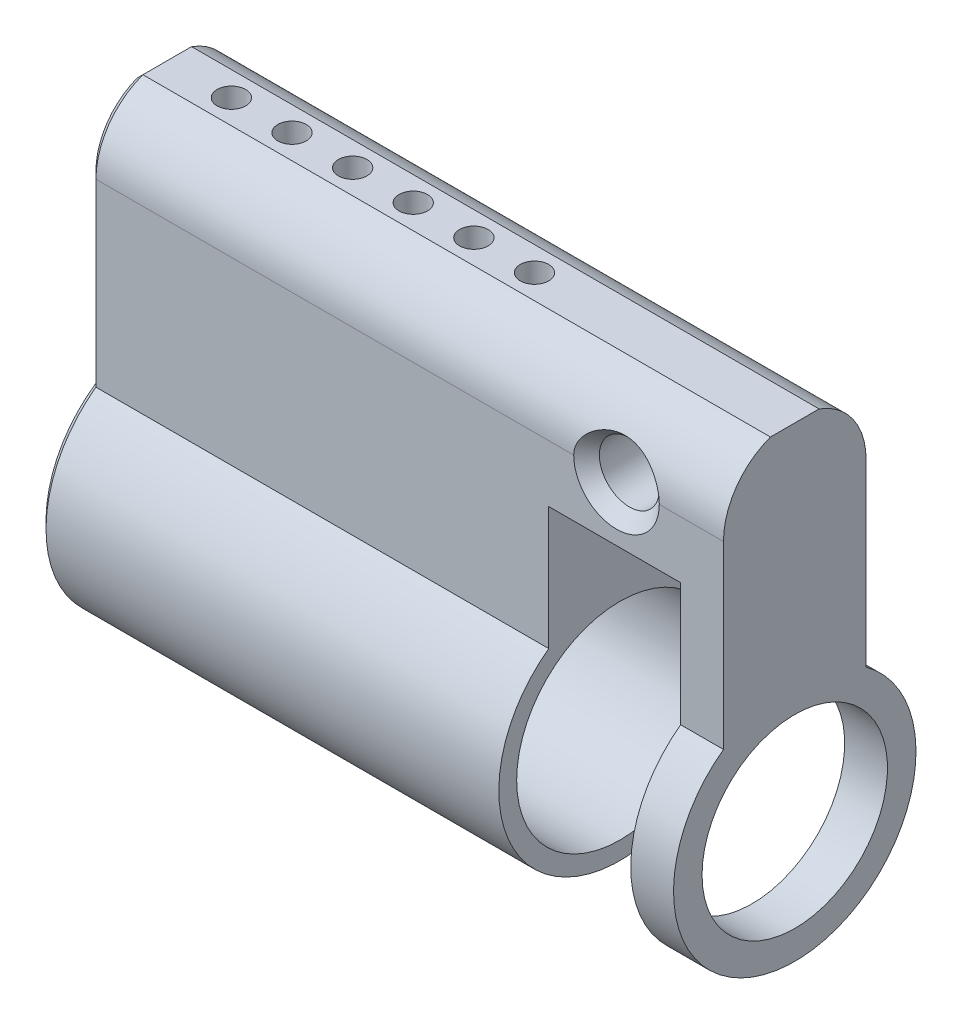
SolidWorks part; units mm, degrees
ref_plane "Front Plane" through (0, 0, 0) normal (0, 0, 1) x (1, 0, 0)
ref_plane "Top Plane" through (0, 0, 0) normal (0, 1, 0) x (1, 0, 0)
ref_plane "Right Plane" through (0, 0, 0) normal (1, 0, 0) x (0, 0, -1)
sketch "Sketch1" plane through (0, 0, 0) normal (1, 0, 0) x (0, 0, -1)
  line L0 (0, 0) -> (0, 19.5) construction
  line L1 (-5, 19.5) -> (5, 19.5) construction
  line L2 (-5, 19.5) -> (-5, 6.8739)
  line L3 (5, 19.5) -> (5, 6.8739)
  line L4 (-1.7059, 24.2) -> (1.7059, 24.2)
  arc A0 (-5, 6.8739) -> (5, 6.8739) centre (0, 0) ccw
  arc A1 (5, 19.5) -> (1.7059, 24.2) centre (0, 19.5) ccw
  arc A3 (-1.7059, 24.2) -> (-5, 19.5) centre (0, 19.5) ccw
  dimension "D1" = 17
  dimension "D2" = 5
  dimension "D3" = 33
  dimension "D5" = 0.3
  dimension "D6" = 3.4117
extrude "euro cylinder outline" add sketch "Sketch1" along normal blind 44.5
sketch "Sketch9" plane through (0, 0, 0) normal (-1, 0, 0) x (0, 0, 1)
  circle A0 centre (0, 0) radius 7.25
  dimension "D1" = 14.5
extrude "bore for core" cut sketch "Sketch9" against normal blind 37
sketch "Sketch2" plane through (0, 0, 0) normal (0, 1, 0) x (1, 0, 0)
  line L0 (0, 5) -> (0, 1.7059) construction
  circle A0 centre (5, 0) radius 1
  dimension "D1" = 2
  dimension "D2" = 5
extrude "hole for pin" cut sketch "Sketch2" along normal blind 35
pattern_linear "LPattern of 6" count 6 spacing 4.25 along (1, 0, 0) of "hole for pin"
sketch "Sketch3" plane through (0, 0, 5) normal (0, 0, 1) x (1, 0, 0)
  line L0 (44.5, 19.5) -> (44.5, 6.8739) construction
  line L1 (32.25, -8.5) -> (41.5, -8.5)
  line L2 (32.25, -8.5) -> (32.25, 15.5)
  line L3 (32.25, 15.5) -> (41.5, 15.5)
  line L4 (41.5, -8.5) -> (41.5, 15.5)
  line L5 (44.5, 24.2) -> (0, 24.2) construction
  dimension "D1" = 3
  dimension "D2" = 9.25
  dimension "D3" = 8.7
  dimension "D4" = 24
extrude "openning" cut sketch "Sketch3" against normal through all and the other way through all
hole_wizard "M5x0.8 mounting hole" positions "Sketch8" profile "Sketch7" tap size "M5x0.8" standard "BSI" end condition through all
sketch "Sketch8" plane through (0, 0, 5) normal (0, 0, 1) x (1, 0, 0)
  line L0 (0, 19.5) -> (0, 6.8739) construction
  line L3 (32.25, 15.5) -> (41.5, 15.5) construction
  point P0 (37, 19.5)
  dimension "D1" = 37
  dimension "D2" = 4
sketch "Sketch7" plane through (37, 19.5, 5) normal (1, 0, 0) x (0, -1, 0)
  line L0 (0, 0) -> (0, 10)
  line L1 (0, 10) -> (3, 10)
  line L2 (2.1, 9.1) -> (2.1, 0.9)
  line L3 (2.1, 0.9) -> (3, 0)
  line L5 (3, 0) -> (0, 0)
  line L6 (-2.1, 0.9) -> (-3, 0) construction
  line L7 (3, 10) -> (2.1, 9.1)
  line L8 (-3, 10) -> (-2.1, 9.1) construction
  line L11 (0, -6.35) -> (0, 107.95) construction
  dimension "Thru Tap Drill Dia." = 4.2
  dimension "Thru Tap Drill Depth" = 10
  dimension "Near C'Sink Dia." = 6
  dimension "Near C'Sink Angle" = 90
  dimension "Far C'Sink Dia." = 6
  dimension "Far C'Sink Angle" = 90
cosmetic thread "Hole Thread2" parameters "D2"=5
chamfer "0.5 x 45 deg" distance 0.5 angle 45 6 edges at (0, 13.1869, 5) (0, -8.5, 0) (0, 22.3697, 4.0945) (0, 24.2, 0) (0, 22.3697, -4.0945) (0, 13.1869, -5)
sketch "Sketch10" plane through (41.5, 0, 0) normal (-1, 0, 0) x (0, 0, 1)
  circle A0 centre (0, 0) radius 6.5
  dimension "D1" = 13
extrude "dia 13 end bit" cut sketch "Sketch10" against normal through all
